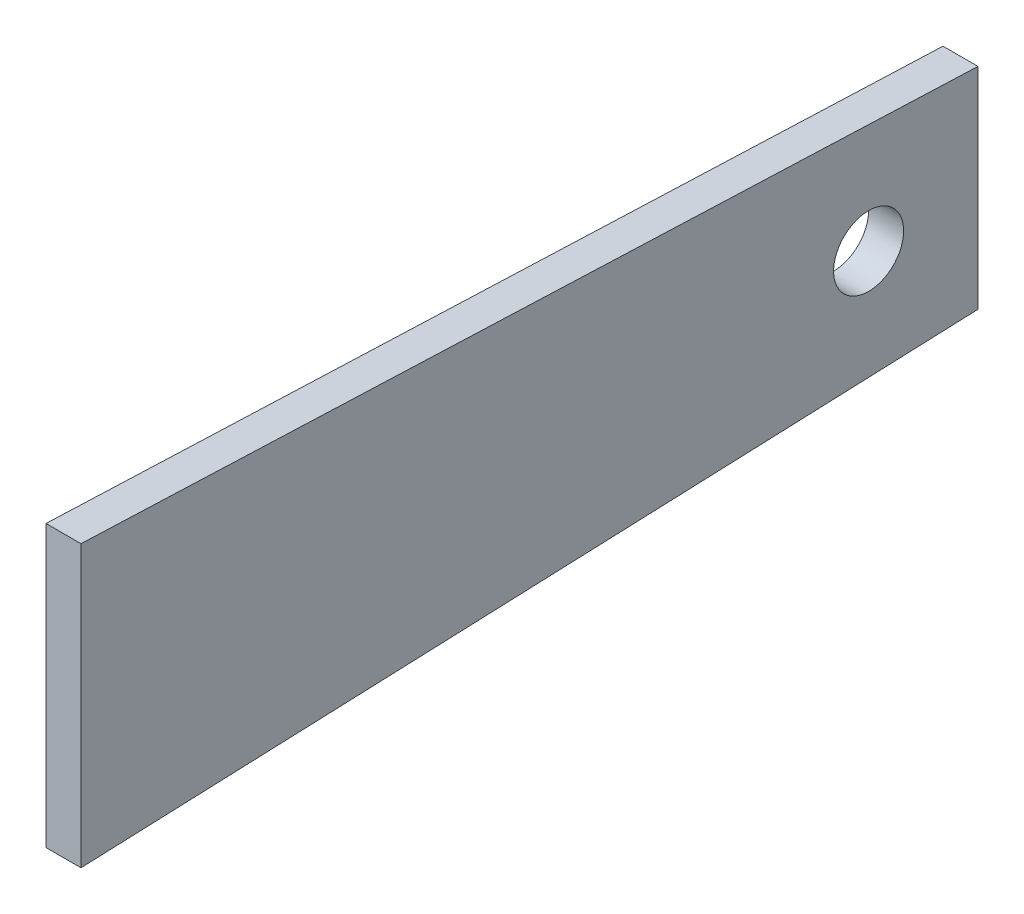
SolidWorks part; units mm, degrees
material "Perspex (TM) GS Acrylic Cast Sheet"
ref_plane "Front Plane" through (0, 0, 0) normal (0, 0, 1) x (1, 0, 0)
ref_plane "Top Plane" through (0, 0, 0) normal (0, 1, 0) x (1, 0, 0)
ref_plane "Right Plane" through (0, 0, 0) normal (1, 0, 0) x (0, 0, -1)
sketch "Sketch1" plane through (0, 0, 0) normal (1, 0, 0) x (0, 0, -1)
  line L0 (-90, 16.0391) -> (-90, -16.0391)
  line L1 (12.5, -12.0194) -> (12.5, 12.0194)
  line L19 (-90, 16.0391) -> (12.5, 12.0194)
  line L20 (-90, -16.0391) -> (12.5, -12.0194)
  circle A0 centre (0, 0) radius 4
  point P18 (0, 0)
  dimension "D1" = 8
  dimension "D5" = 90
  dimension "D8" = 12.5
  dimension "D6" = 4.492
  dimension "D7" = 87.754
extrude "Boss-Extrude1" add sketch "Sketch1" along normal blind 4
sketch "Sketch2" plane through (4, 0, 0) normal (1, 0, 0) x (0, 0, -1)
  line L0 (0, 0) -> (-90, 0) construction
  line L1 (-90, 16.0391) -> (-90, -16.0391) construction
